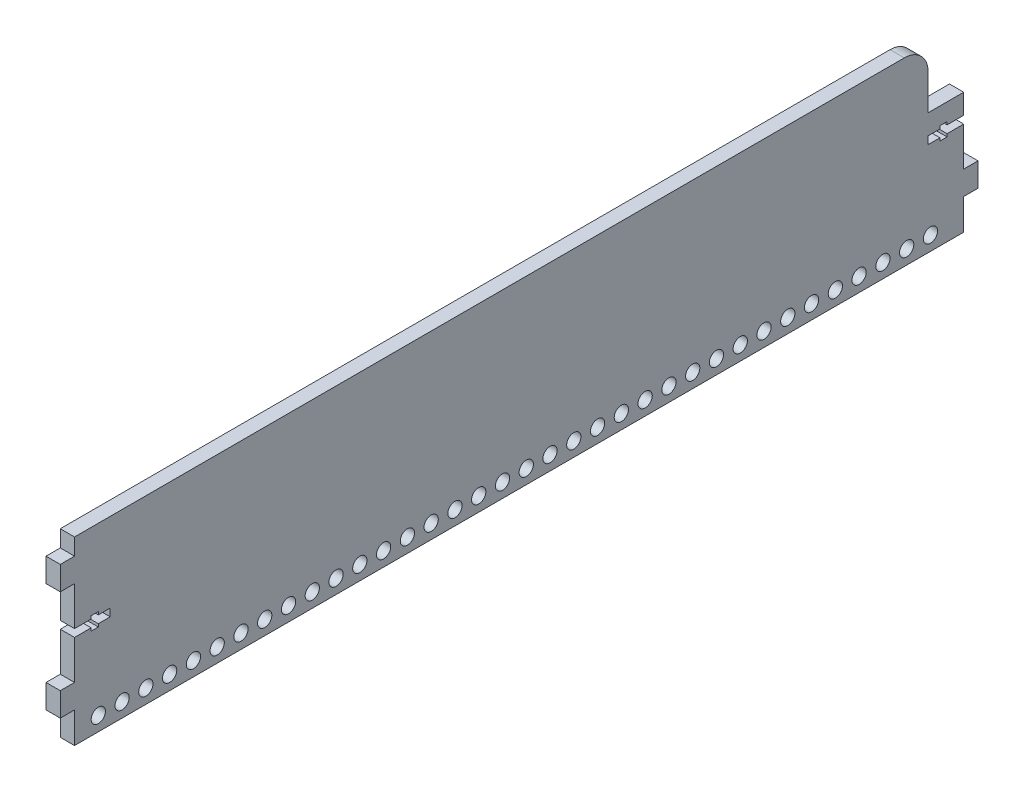
SolidWorks part; units mm, degrees
ref_plane "Front Plane" through (0, 0, 0) normal (0, 0, 1) x (1, 0, 0)
ref_plane "Top Plane" through (0, 0, 0) normal (0, 1, 0) x (1, 0, 0)
ref_plane "Right Plane" through (0, 0, 0) normal (1, 0, 0) x (0, 0, -1)
sketch "Sketch1" plane through (0, 0, 0) normal (1, 0, 0) x (0, 0, -1)
  line L1 (-187, -40) -> (187, -40)
  line L2 (-187, -40) -> (-187, 40)
  line L3 (-187, 40) -> (187, 40)
  line L4 (187, -40) -> (187, 40)
  line L5 (-187, -40) -> (187, 40) construction
  line L6 (-187, 40) -> (187, -40) construction
  point P0 (0, 0)
  dimension "D1" = 80
  dimension "D2" = 374
extrude "Boss-Extrude1" add sketch "Sketch1" along normal blind 6
sketch "Sketch4" plane through (0, 0, 187) normal (0, 0, 1) x (1, 0, 0)
  line L1 (6, 29) -> (0, 29) construction
  line L2 (6, 19) -> (6, 29) construction
  line L3 (0, 29) -> (0, 19) construction
  line L4 (0, 19) -> (6, 19) construction
  line L7 (6, -17) -> (0, -17) construction
  line L8 (6, -27) -> (6, -17) construction
  line L9 (0, -17) -> (0, -27) construction
  line L10 (0, -27) -> (6, -27) construction
  line L13 (6, 29) -> (0, 29)
  line L14 (6, 19) -> (6, 29)
  line L15 (0, 29) -> (0, 19)
  line L16 (0, 19) -> (6, 19)
  line L17 (6, -17) -> (0, -17)
  line L18 (6, -27) -> (6, -17)
  line L19 (0, -17) -> (0, -27)
  line L20 (0, -27) -> (6, -27)
extrude "Boss-Extrude2" add sketch "Sketch4" along normal blind 6
sketch "Sketch5" plane through (0, 0, 0) normal (-1, 0, 0) x (0, 0, 1)
  line L0 (187, 19) -> (187, -17) construction
  line L7 (0, 0) -> (0, -20.5925) construction
  line L8 (-187, 2.6) -> (-180, 2.6)
  line L9 (-177, 3.8) -> (-180, 3.8)
  line L10 (-177, 2.6) -> (-172, 2.6)
  line L11 (-172, -0.6) -> (-172, 2.6)
  line L12 (-177, -0.6) -> (-172, -0.6)
  line L13 (-177, -1.8) -> (-180, -1.8)
  line L14 (-187, -0.6) -> (-180, -0.6)
  line L15 (-180, -1.8) -> (-180, -0.6)
  line L16 (-180, 2.6) -> (-180, 3.8)
  line L17 (-177, 2.6) -> (-177, 3.8)
  line L18 (-177, -1.8) -> (-177, -0.6)
  line L19 (193, -0.6) -> (193, 2.6) construction
  line L20 (193, -0.6) -> (193, 2.6)
  line L21 (193, 1) -> (146.4296, 1) construction
  line L25 (187, -0.6) -> (187, 2.6)
  line L26 (177, -1.8) -> (177, -0.6)
  line L27 (177, 2.6) -> (177, 3.8)
  line L28 (180, 2.6) -> (180, 3.8)
  line L29 (180, -1.8) -> (180, -0.6)
  line L30 (187, -0.6) -> (180, -0.6)
  line L31 (177, -1.8) -> (180, -1.8)
  line L32 (177, -0.6) -> (172, -0.6)
  line L33 (172, -0.6) -> (172, 2.6)
  line L34 (177, 2.6) -> (172, 2.6)
  line L35 (177, 3.8) -> (180, 3.8)
  line L36 (187, 2.6) -> (180, 2.6)
  line L37 (-187, -0.6) -> (-187, 2.6)
  line L38 (-193, -0.6) -> (-193, 2.6)
  point P0 (187, 1)
  dimension "D1" = 15
  dimension "D2" = 5.6
  dimension "D3" = 3.2
  dimension "D4" = 7
  dimension "D5" = 3
extrude "Cut-Extrude3" cut sketch "Sketch5" against normal up to next contours L25 L36 L28 L35 L27 L34 L33 L32 L26 L31 L29 L30 | L37 L14 L15 L13 L18 L12 L11 L10 L17 L9 L16 L8 region at (0, 1, -179.3696) region at (0, 1, 179.3696)
sketch "Sketch7" plane through (0, 0, -187) normal (0, 0, -1) x (-1, 0, 0)
  line L6 (-6, -17) -> (0, -17)
  line L7 (-6, -17) -> (-6, -27)
  line L8 (-6, -27) -> (0, -27)
  line L9 (0, -17) -> (0, -27)
  line L15 (-6, -40) -> (-6, -0.6) construction
  line L16 (0, -40) -> (0, -0.6) construction
  line L17 (-6, -17) -> (0, -17) construction
  line L18 (0, -27) -> (-6, -27) construction
extrude "Boss-Extrude3" add sketch "Sketch7" along normal blind 6
sketch "Sketch8" plane through (0, 40, 0) normal (0, 1, 0) x (1, 0, 0)
  line L1 (0, 187) -> (6, 187)
  line L2 (0, 187) -> (0, -187)
  line L3 (0, -187) -> (6, -187)
  line L4 (6, 187) -> (6, -187)
extrude "Cut-Extrude4" cut sketch "Sketch8" against normal blind 4
sketch "Sketch9" plane through (0, 36, 0) normal (0, 1, 0) x (1, 0, 0)
  line L0 (0, 187) -> (0, -187) construction
  line L1 (0, 187) -> (6, 187)
  line L2 (0, 187) -> (0, 172)
  line L3 (0, 172) -> (6, 172)
  line L4 (6, 187) -> (6, 172)
  line L5 (6, -187) -> (6, 187) construction
  dimension "D2" = 15
extrude "Cut-Extrude5" cut sketch "Sketch9" against normal blind 25
fillet "Fillet1" radius 10 1 edges at (3, 36, -172)
sketch "Sketch10" plane through (0, 0, 0) normal (-1, 0, 0) x (0, 0, 1)
  line L0 (187, -40) -> (-187, -40) construction
  line L1 (187, -27) -> (187, -40) construction
  circle A0 centre (177, -34) radius 3
  circle A1 centre (167, -34) radius 3
  circle A2 centre (157, -34) radius 3
  circle A3 centre (147, -34) radius 3
  circle A4 centre (137, -34) radius 3
  circle A5 centre (127, -34) radius 3
  circle A6 centre (117, -34) radius 3
  circle A7 centre (107, -34) radius 3
  circle A8 centre (97, -34) radius 3
  circle A9 centre (87, -34) radius 3
  circle A10 centre (77, -34) radius 3
  circle A11 centre (67, -34) radius 3
  circle A12 centre (57, -34) radius 3
  circle A13 centre (47, -34) radius 3
  circle A14 centre (37, -34) radius 3
  circle A15 centre (27, -34) radius 3
  circle A16 centre (17, -34) radius 3
  circle A17 centre (7, -34) radius 3
  circle A18 centre (-3, -34) radius 3
  circle A19 centre (-13, -34) radius 3
  circle A20 centre (-23, -34) radius 3
  circle A21 centre (-33, -34) radius 3
  circle A22 centre (-43, -34) radius 3
  circle A23 centre (-53, -34) radius 3
  circle A24 centre (-63, -34) radius 3
  circle A25 centre (-73, -34) radius 3
  circle A26 centre (-83, -34) radius 3
  circle A27 centre (-93, -34) radius 3
  circle A28 centre (-103, -34) radius 3
  circle A29 centre (-113, -34) radius 3
  circle A30 centre (-123, -34) radius 3
  circle A31 centre (-133, -34) radius 3
  circle A32 centre (-143, -34) radius 3
  circle A33 centre (-153, -34) radius 3
  circle A34 centre (-163, -34) radius 3
  circle A35 centre (-173, -34) radius 3
  dimension "D1" = 6
  dimension "D2" = 6
  dimension "D3" = 10
  dimension "D4" = 36
extrude "Cut-Extrude6" cut sketch "Sketch10" against normal up to next (6 mm away)
